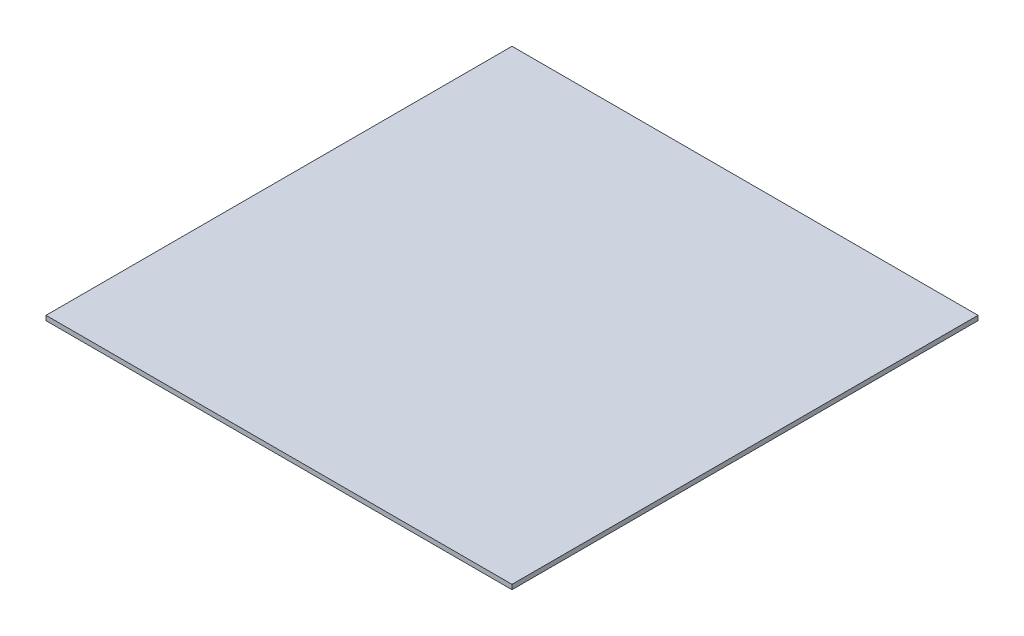
SolidWorks part; units mm, degrees
ref_plane "Plan de face" through (0, 0, 0) normal (0, 0, 1) x (1, 0, 0)
ref_plane "Plan de dessus" through (0, 0, 0) normal (0, 1, 0) x (1, 0, 0)
ref_plane "Plan de droite" through (0, 0, 0) normal (1, 0, 0) x (0, 0, -1)
sketch "Esquisse1" plane through (0, 0, 0) normal (0, 1, 0) x (1, 0, 0)
  line L1 (-150, -150) -> (150, -150)
  line L2 (-150, -150) -> (-150, 150)
  line L3 (-150, 150) -> (150, 150)
  line L4 (150, -150) -> (150, 150)
  line L5 (-150, -150) -> (150, 150) construction
  line L6 (-150, 150) -> (150, -150) construction
  point P0 (0, 0)
  dimension "D1" = 300
extrude "Boss.-Extru.1" add sketch "Esquisse1" along normal blind 3
